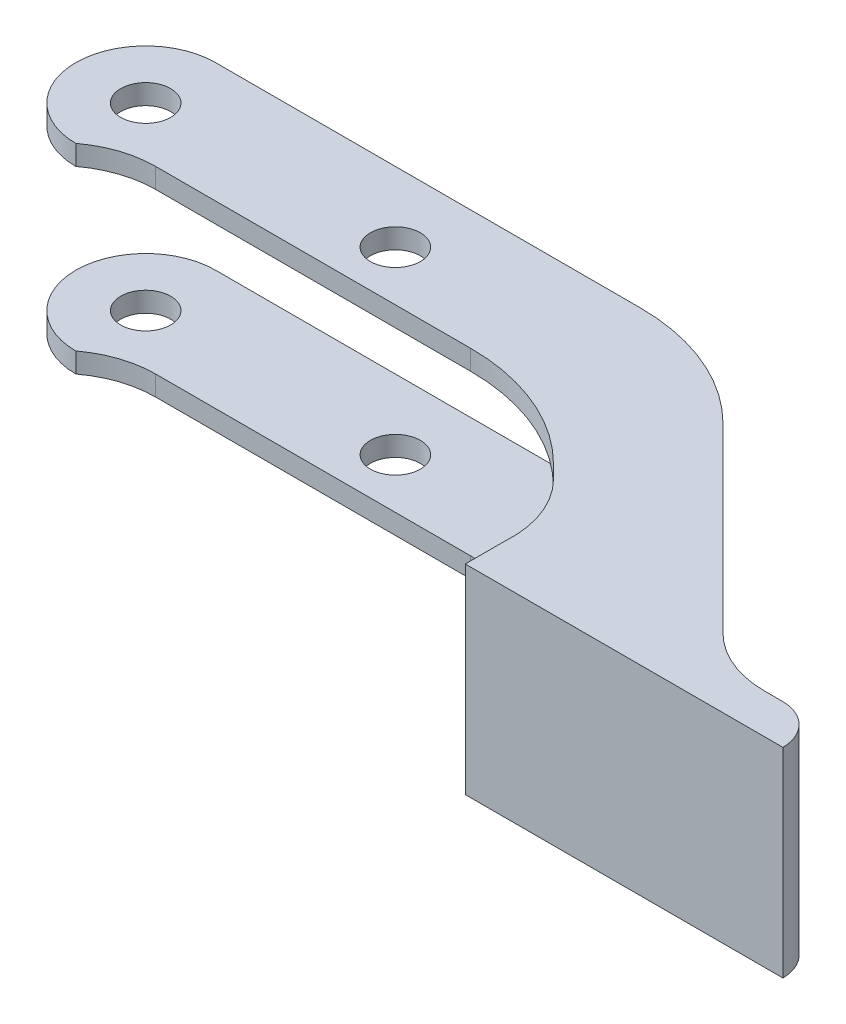
SolidWorks part; units mm, degrees
ref_plane "Front Plane" through (0, 0, 0) normal (0, 0, 1) x (1, 0, 0)
ref_plane "Top Plane" through (0, 0, 0) normal (0, 1, 0) x (1, 0, 0)
ref_plane "Right Plane" through (0, 0, 0) normal (1, 0, 0) x (0, 0, -1)
sketch "Sketch1" plane through (0, 0, 0) normal (0, 1, 0) x (1, 0, 0)
  line L0 (0, 0) -> (25, 0) construction
  line L1 (0, 7) -> (25, 7)
  line L2 (0, -7) -> (25, -7)
  arc A0 (0, 7) -> (0, -7) centre (0, 0) ccw
  arc A1 (25, -7) -> (25, 7) centre (25, 0) ccw
  circle A2 centre (0, 0) radius 2.5
  circle A3 centre (25, 0) radius 2.5
  point P3 (12.5, 0)
  dimension "D1" = 5
  dimension "D2" = 5
  dimension "D3" = 25
  dimension "D4" = 14
extrude "Boss-Extrude1" add sketch "Sketch1" along normal blind 2
sketch "Sketch2" plane through (0, 0, 0) normal (0, -1, 0) x (1, 0, 0)
  line L0 (25, 7) -> (45, 7) construction
  line L1 (25, -7) -> (45, -7) construction
  line L2 (45, 7) -> (61.9706, 23.9706) construction
  line L3 (61.9706, 23.9706) -> (71.8701, 14.0711) construction
  line L4 (71.8701, 14.0711) -> (50.799, -7) construction
  line L5 (50.799, -7) -> (45, -7) construction
  dimension "D1" = 20
  dimension "D2" = 14
  dimension "D3" = 24
  dimension "D4" = 135
sketch "Sketch3" plane through (0, 0, 0) normal (0, -1, 0) x (-1, 0, 0)
  line L0 (-25, -7) -> (-36.7157, -7)
  line L1 (-50.8579, -12.8579) -> (-61.9706, -23.9706)
  line L2 (-61.9706, -23.9706) -> (-81.7696, -23.9706)
  line L3 (-71.8701, -14.0711) -> (-81.7696, -23.9706)
  line L4 (-71.8701, -14.0711) -> (-56.6569, 1.1421)
  line L5 (-42.5147, 7) -> (-25, 7)
  arc A0 (-42.5147, 7) -> (-56.6569, 1.1421) centre (-42.5147, -13) ccw
  arc A1 (-36.7157, -7) -> (-50.8579, -12.8579) centre (-36.7157, -27) ccw
  arc A2 (-25, 7) -> (-25, -7) centre (-25, 0) ccw
  point P15 (-50.799, 7)
  point P18 (-45, -7)
  dimension "D1" = 20
  dimension "D2" = 20
extrude "Boss-Extrude2" add sketch "Sketch3" against normal blind 2
sketch "Sketch4" plane through (0, 2, 0) normal (0, 1, 0) x (1, 0, 0)
  line L10 (55.9706, -20.004) -> (87.7696, -20.004)
  line L11 (55.9706, -20.004) -> (55.9706, -23.9706)
  line L12 (55.9706, -23.9706) -> (87.7696, -23.9706)
  line L13 (87.7696, -20.004) -> (87.7696, -23.9706)
  dimension "D1" = 6
  dimension "D2" = 6
extrude "Boss-Extrude3" add sketch "Sketch4" along normal blind 18 and the other way blind 2
sketch "Sketch8" plane through (0, 0, 0) normal (0, -1, 0) x (1, 0, 0)
  line L0 (0, 0) -> (25, 0) construction
  line L1 (0, 5) -> (25, 5)
  line L4 (25, 5) -> (37.5442, 5)
  line L5 (60.8324, 20.004) -> (51.6863, 10.8579)
  line L6 (58.004, 20.004) -> (50.8579, 12.8579) construction
  line L7 (58.004, 20.004) -> (60.8324, 20.004)
  line L8 (58.004, 20.004) -> (50.5285, 12.6973)
  line L9 (36.5488, 7) -> (0, 7)
  line L10 (0, 7) -> (0, 5)
  arc A2 (50.5285, 12.6973) -> (36.5488, 7) centre (36.5488, 27) cw
  arc A3 (51.6863, 10.8579) -> (37.5442, 5) centre (37.5442, 25) cw
  point P4 (12.5, 0)
  dimension "D3" = 20
  dimension "D4" = 20
  dimension "D2" = 2
ref_plane "Plane1" through (0, 10, 0) normal (0, 1, 0) x (1, 0, 0)
mirror "Mirror1" about plane through (0, 10, 0) normal (0, 1, 0) of "Boss-Extrude2", "Boss-Extrude1"
sketch "Sketch6" plane through (0, 20, 0) normal (0, 1, 0) x (1, 0, 0)
  line L0 (25, 0) -> (0, 0) construction
  line L1 (25, -7) -> (0, -7)
  line L2 (25, 7) -> (0, 7)
  arc A0 (25, -7) -> (25, 7) centre (25, 0) ccw
  arc A1 (0, 7) -> (0, -7) centre (0, 0) ccw
  circle A2 centre (0, 0) radius 2.5
  circle A3 centre (25, 0) radius 2.5
  point P4 (12.5, 0)
  dimension "D1" = 14
extrude "Boss-Extrude5" add sketch "Sketch6" against normal blind 2
fillet "Fillet1" radius 10 2 edges at (58.004, 1, 20.004) (58.004, 19, 20.004)
fillet "Fillet2" radius 10 2 edges at (77.803, 19, 20.004) (77.803, 1, 20.004)
fillet "Fillet4" radius 4 1 edges at (87.7696, 10, 20.004)
sketch "Sketch7" plane through (0, 2, 0) normal (0, 1, 0) x (1, 0, 0)
  line L0 (0, 0) -> (25, 0) construction
  line L1 (0, 7) -> (25, 7)
  line L3 (0, 0) -> (25, 0) construction
  line L4 (0, 5) -> (25, 5)
  line L6 (-7, 0) -> (-5, 0)
  line L9 (25, 7) -> (42.5147, 7)
  line L10 (74.8741, -17.0751) -> (56.6569, 1.1421)
  line L11 (74.9746, -20.004) -> (81.9451, -20.004)
  line L16 (25, 5) -> (41.6863, 5)
  line L17 (71.0679, -16.0974) -> (55.8284, -0.8579)
  line L19 (71.0679, -16.0974) -> (74.9746, -20.004)
  arc A0 (0, 7) -> (-7, 0) centre (0, 0) ccw
  arc A2 (0, 5) -> (-5, 0) centre (0, 0) ccw
  arc A4 (56.6569, 1.1421) -> (42.5147, 7) centre (42.5147, -13) ccw
  arc A5 (55.8284, -0.8579) -> (41.6863, 5) centre (41.6863, -15) ccw
  spline S0 degree 3 poles (74.8741, -17.0751) (76.6185, -18.7453) (78.6848, -19.8172) (81.9451, -20.004) knots 0 0 0 0 1 1 1 1
  point P4 (12.5, 0)
  point P12 (12.5, 0)
  dimension "D1" = 7
  dimension "D4" = 20
  dimension "D5" = 20
  dimension "D2" = 2
  dimension "D3" = 2
extrude "Cut-Extrude1" cut sketch "Sketch8" against normal through all
sketch "Sketch9" plane through (0, 0, 0) normal (0, -1, 0) x (1, 0, 0)
  line L1 (58.004, 20.004) -> (51.7659, 20.004)
  line L2 (58.004, 20.004) -> (58.004, 18.0864)
  line L3 (58.004, 18.0864) -> (51.7659, 18.0864)
  line L4 (51.7659, 20.004) -> (51.7659, 18.0864)
extrude "Cut-Extrude2" cut sketch "Sketch9" against normal through all
fillet "Fillet5" radius 10 2 edges at (60.8324, 19, 20.004) (60.8324, 1, 20.004)
fillet "Fillet6" radius 10 2 edges at (0, 19, 5) (0, 1, 5)
sketch "Sketch10" plane through (0, 2, 0) normal (0, 1, 0) x (1, 0, 0)
  circle A0 centre (46.1591, 0) radius 3
  dimension "D1" = 6
extrude "Boss-Extrude6" add sketch "Sketch10" along normal through all
